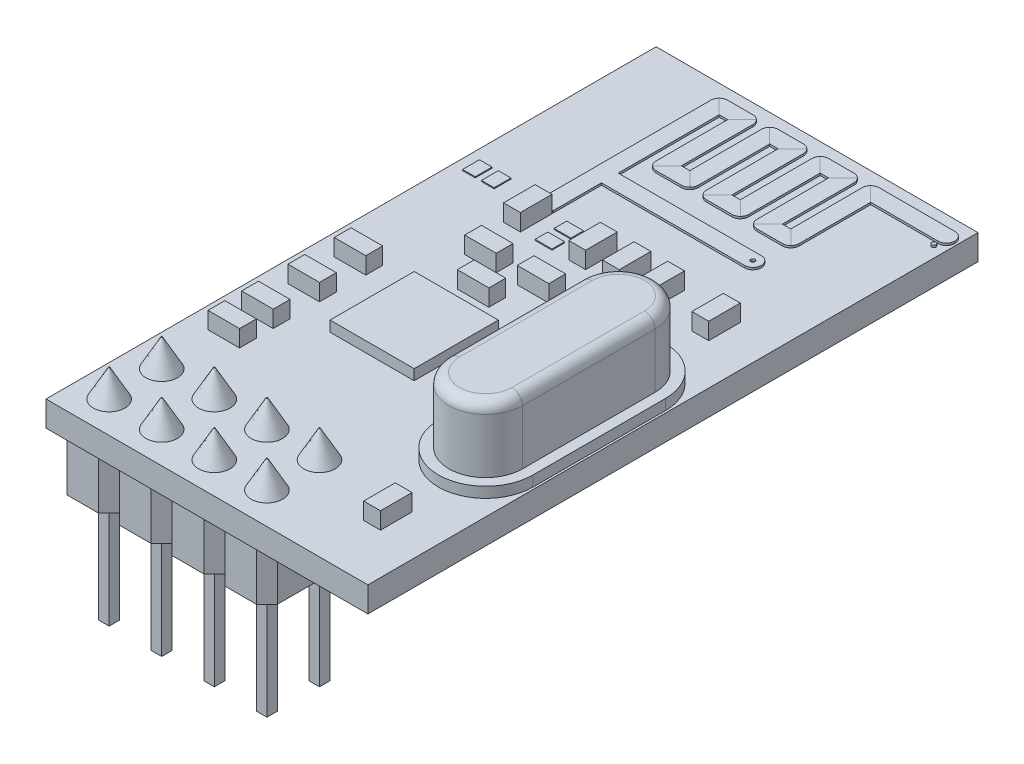
SolidWorks part; units mm, degrees
material "ABS"
ref_plane "정면" through (0, 0, 0) normal (0, 0, 1) x (1, 0, 0)
ref_plane "윗면" through (0, 0, 0) normal (0, 1, 0) x (1, 0, 0)
ref_plane "우측면" through (0, 0, 0) normal (1, 0, 0) x (0, 0, -1)
sketch "스케치1" plane through (0, 0, 0) normal (0, 1, 0) x (1, 0, 0)
  line L1 (7.65, -14.5) -> (-7.65, -14.5)
  line L2 (7.65, -14.5) -> (7.65, 14.5)
  line L3 (7.65, 14.5) -> (-7.65, 14.5)
  line L4 (-7.65, -14.5) -> (-7.65, 14.5)
  line L5 (7.65, -14.5) -> (-7.65, 14.5) construction
  line L6 (7.65, 14.5) -> (-7.65, -14.5) construction
  point P0 (0, 0)
  dimension "D1" = 15.3
  dimension "D2" = 29
extrude "보스-돌출1" add sketch "스케치1" along normal blind 1.2
sketch "스케치2" plane through (0, 1.2, 0) normal (0, 1, 0) x (1, 0, 0)
  line L0 (-7.65, 14.5) -> (-7.65, -14.5) construction
  line L1 (-7.65, -14.5) -> (7.65, -14.5) construction
  circle A0 centre (-6.15, -13) radius 0.75
  point P2 (-6.2469, -13.1386)
  dimension "D1" = 1.5
  dimension "D2" = 1.5
  dimension "D3" = 1.5
extrude "보스-돌출2" add sketch "스케치2" along normal blind 1.3
chamfer "모따기1" distance 1.3 angle 29 1 edges at (-6.15, 2.5, 13.75) first distance on face at (-6.15, 2.5, 13.75)
pattern_linear "선형 패턴1" count 4 spacing 2.5 along (1, 0, 0) count 2 spacing 2.5 along (0, 0, -1) of "보스-돌출2", "모따기1"
sketch "스케치3" plane through (0, 1.2, 0) normal (0, 1, 0) x (1, 0, 0)
  line L0 (-3.65, 5.2) -> (-3.65, 13.5)
  line L1 (-3.65, 13.5) -> (-2.45, 13.5)
  line L2 (-2.45, 13.5) -> (-2.45, 9.7)
  line L3 (-2.45, 9.7) -> (-1.25, 9.7)
  line L4 (-1.25, 9.7) -> (-1.25, 13.5)
  line L5 (-1.25, 13.5) -> (-0.05, 13.5)
  line L6 (-0.05, 13.5) -> (-0.05, 9.7)
  line L7 (-0.05, 9.7) -> (1.15, 9.7)
  line L8 (1.15, 9.7) -> (1.15, 13.5)
  line L9 (1.15, 13.5) -> (2.35, 13.5)
  line L10 (2.35, 13.5) -> (2.35, 9.7)
  line L11 (2.35, 9.7) -> (3.55, 9.7)
  line L12 (3.55, 9.7) -> (3.55, 13.5)
  line L13 (3.55, 13.5) -> (7.55, 13.5)
  line L14 (7.65, 14.5) -> (-7.65, 14.5) construction
  line L15 (7.65, -14.5) -> (7.65, 14.5) construction
  line L17 (-7.65, 14.5) -> (-7.65, -14.5) construction
  point P15 (-3.5057, 3.4598)
  point P17 (-2.4342, 13.6732)
  point P18 (6.8569, 13.6584)
  point P23 (4.6486, 13.5)
  point P24 (-3.5225, 13.5)
  point P25 (6.2398, 13.5)
  point P26 (4.1946, 13.5)
  point P27 (-3.3928, 13.4558)
  point P28 (2.6625, 9.4177)
  point P29 (0, 0)
  point P30 (-3.7935, 13.5)
  point P33 (-2.177, 13.5)
  point P34 (0, 13.5)
  point P35 (-0.899, 13.5)
  point P36 (1.3401, 13.5)
  point P37 (-1.1799, 13.5)
  dimension "D1" = 1
  dimension "D2" = 4
  dimension "D3" = 0.1
  dimension "D4" = 3.8
  dimension "D5" = 9.3
  dimension "D6" = 4
ref_plane "평면1" through (7.55, 0, 0) normal (1, 0, 0) x (0, 0, -1)
sketch "스케치4" plane through (7.55, 0, 0) normal (1, 0, 0) x (0, 0, -1)
  line L0 (13.5, 1.2) -> (9.7, 1.2) construction
  line L1 (13.9, 1.1) -> (13.1, 1.1)
  line L2 (13.9, 1.1) -> (13.9, 1.3)
  line L3 (13.9, 1.3) -> (13.1, 1.3)
  line L4 (13.1, 1.1) -> (13.1, 1.3)
  line L5 (13.9, 1.1) -> (13.1, 1.3) construction
  line L6 (13.9, 1.3) -> (13.1, 1.1) construction
  line L7 (-14.5, 1.2) -> (14.5, 1.2) construction
  point P0 (13.5, 1.2)
  point P9 (13.6993, 1.2)
  dimension "D1" = 0.1
  dimension "D2" = 0.8
sweep "스윕1" add profiles "스케치4" path "스케치3"
fillet "필렛1" radius 0.4 15 edges at (2.75, 1.25, -13.9) (0.75, 1.25, -13.9) (0.35, 1.25, -13.9) (-1.65, 1.25, -13.9) (-2.05, 1.25, -13.9) (-4.05, 1.25, -13.9) (-2.85, 1.25, -9.3) (-0.85, 1.25, -9.3) (-0.45, 1.25, -9.3) (1.55, 1.25, -9.3) (1.95, 1.25, -9.3) (3.95, 1.25, -9.3) (3.15, 1.25, -13.9) (7.55, 1.25, -13.1) (7.55, 1.25, -13.9)
sketch "스케치6" plane through (0, 1.2, 0) normal (0, 1, 0) x (1, 0, 0)
  line L0 (-3.25, 5.2) -> (-3.25, 13.1) construction
  line L1 (-3.25, 8.3) -> (3.55, 8.3)
  line L2 (-3.25, 8.3) -> (-3.25, 7.5)
  line L3 (-3.25, 7.5) -> (3.55, 7.5)
  line L5 (7.65, 14.5) -> (-7.65, 14.5) construction
  line L6 (3.95, 9.7) -> (3.95, 13.1) construction
  arc A0 (3.55, 7.5) -> (3.55, 8.3) centre (3.55, 7.9) ccw
  point P8 (0, 0)
  dimension "D1" = 0.8
  dimension "D2" = 7
extrude "보스-돌출3" add sketch "스케치6" along normal up to surface (0.1 mm away) up to face at (-3.7122, 1.3, -10.1589)
sketch "스케치7" plane through (0, 1.2, 0) normal (0, 1, 0) x (1, 0, 0)
  line L0 (7.15, 13.5) -> (7.15, 12.9) construction
  circle A0 centre (7.15, 12.9) radius 0.1
  point P2 (7.15, 13.5)
  dimension "D1" = 0.2
  dimension "D2" = 0.6
extrude "보스-돌출4" add sketch "스케치7" along normal up to surface (0.1 mm away) up to face at (5.4619, 1.3, -13.5518)
sketch "스케치8" plane through (0, 1.3, 0) normal (0, 1, 0) x (1, 0, 0)
  circle A0 centre (3.55, 7.9) radius 0.1
  circle A2 centre (7.15, 12.9) radius 0.1 construction
extrude "컷-돌출1" cut sketch "스케치8" against normal up to surface (0.1 mm away) up to face at (7.15, 1.2, -12.8)
sketch "스케치9" plane through (0, 1.2, 0) normal (0, 1, 0) x (1, 0, 0)
  line L0 (7.65, -14.5) -> (7.65, 14.5) construction
  line L2 (3.55, -0.25) -> (3.55, -6.55)
  line L4 (7.05, -0.25) -> (7.05, -6.55)
  line L5 (-7.65, -14.5) -> (7.65, -14.5) construction
  arc A0 (7.05, -0.25) -> (3.55, -0.25) centre (5.3, -0.25) ccw
  arc A1 (3.55, -6.55) -> (7.05, -6.55) centre (5.3, -6.55) ccw
  point P5 (5.3, 1.5)
  point P7 (5.3, -8.3)
  point P12 (6.65, -0.5904)
  point P13 (0, 0)
  point P14 (0, 0)
  dimension "D1" = 9.8
  dimension "D2" = 3.5
  dimension "D3" = 4.1
  dimension "D4" = 16
extrude "보스-돌출5" add sketch "스케치9" along normal blind 3.6
sketch "스케치10" plane through (0, 1.2, 0) normal (0, 1, 0) x (1, 0, 0)
  line L2 (3.05, -0.25) -> (3.05, -6.55)
  line L4 (7.55, -0.25) -> (7.55, -6.55)
  arc A0 (7.55, -0.25) -> (3.05, -0.25) centre (5.3, -0.25) ccw
  arc A1 (3.05, -6.55) -> (7.55, -6.55) centre (5.3, -6.55) ccw
  arc A2 (3.55, -6.55) -> (7.05, -6.55) centre (5.3, -6.55) ccw construction
  point P1 (4.9, -0.25)
  point P8 (7.1253, 0.2214)
  point P9 (0, 0)
  point P10 (2.65, -7.2177)
  point P11 (0, 0)
  dimension "D1" = 4.5
extrude "보스-돌출6" add sketch "스케치10" along normal blind 0.5
fillet "필렛2" radius 0.5 4 edges at (7.05, 4.8, 3.4) (5.3, 4.8, 8.3) (3.55, 4.8, 3.4) (5.3, 4.8, -1.5)
sketch "스케치11" plane through (0, 1.2, 0) normal (0, 1, 0) x (1, 0, 0)
  line L0 (-7.65, 14.5) -> (-7.65, -14.5) construction
  line L1 (-3.65, -1) -> (0.35, -1)
  line L2 (-3.65, -1) -> (-3.65, -5)
  line L3 (-3.65, -5) -> (0.35, -5)
  line L4 (0.35, -1) -> (0.35, -5)
  line L5 (-7.65, -14.5) -> (7.65, -14.5) construction
  dimension "D1" = 4
  dimension "D2" = 8
  dimension "D3" = 13.5
extrude "보스-돌출7" add sketch "스케치11" along normal blind 0.5
sketch "스케치12" plane through (0, 1.2, 0) normal (0, 1, 0) x (1, 0, 0)
  line L1 (-5.15, -7.8) -> (-6.65, -7.8)
  line L2 (-5.15, -7.8) -> (-5.15, -7)
  line L3 (-5.15, -7) -> (-6.65, -7)
  line L4 (-6.65, -7.8) -> (-6.65, -7)
  line L5 (-5.15, -7.8) -> (-6.65, -7) construction
  line L6 (-5.15, -7) -> (-6.65, -7.8) construction
  line L7 (-5.15, -6.2) -> (-6.65, -6.2)
  line L8 (-5.15, -6.2) -> (-5.15, -5.4)
  line L9 (-5.15, -5.4) -> (-6.65, -5.4)
  line L10 (-6.65, -6.2) -> (-6.65, -5.4)
  line L11 (-5.15, -6.2) -> (-6.65, -5.4) construction
  line L12 (-5.15, -5.4) -> (-6.65, -6.2) construction
  line L13 (-5.15, -4) -> (-6.65, -4)
  line L14 (-5.15, -4) -> (-5.15, -3.2)
  line L15 (-5.15, -3.2) -> (-6.65, -3.2)
  line L16 (-6.65, -4) -> (-6.65, -3.2)
  line L17 (-5.15, -4) -> (-6.65, -3.2) construction
  line L18 (-5.15, -3.2) -> (-6.65, -4) construction
  line L19 (-5.15, -1.8) -> (-6.65, -1.8)
  line L20 (-5.15, -1.8) -> (-5.15, -1)
  line L21 (-5.15, -1) -> (-6.65, -1)
  line L22 (-6.65, -1.8) -> (-6.65, -1)
  line L23 (-5.15, -1.8) -> (-6.65, -1) construction
  line L24 (-5.15, -1) -> (-6.65, -1.8) construction
  line L25 (-0.9, -0.2) -> (-2.4, -0.2)
  line L26 (-0.9, -0.2) -> (-0.9, 0.6)
  line L27 (-0.9, 0.6) -> (-2.4, 0.6)
  line L28 (-2.4, -0.2) -> (-2.4, 0.6)
  line L29 (-0.9, -0.2) -> (-2.4, 0.6) construction
  line L30 (-0.9, 0.6) -> (-2.4, -0.2) construction
  line L31 (-2.15, 1.4) -> (-3.65, 1.4)
  line L32 (-2.15, 1.4) -> (-2.15, 2.2)
  line L33 (-2.15, 2.2) -> (-3.65, 2.2)
  line L34 (-3.65, 1.4) -> (-3.65, 2.2)
  line L35 (-2.15, 1.4) -> (-3.65, 2.2) construction
  line L36 (-2.15, 2.2) -> (-3.65, 1.4) construction
  line L37 (0.35, 1.4) -> (-1.15, 1.4)
  line L38 (0.35, 1.4) -> (0.35, 2.2)
  line L39 (0.35, 2.2) -> (-1.15, 2.2)
  line L40 (-1.15, 1.4) -> (-1.15, 2.2)
  line L41 (0.35, 1.4) -> (-1.15, 2.2) construction
  line L42 (0.35, 2.2) -> (-1.15, 1.4) construction
  line L43 (5.7, 3.65) -> (4.9, 3.65)
  line L44 (5.7, 3.65) -> (5.7, 5.15)
  line L45 (5.7, 5.15) -> (4.9, 5.15)
  line L46 (4.9, 3.65) -> (4.9, 5.15)
  line L47 (5.7, 3.65) -> (4.9, 5.15) construction
  line L48 (5.7, 5.15) -> (4.9, 3.65) construction
  line L49 (3.05, 3.65) -> (2.25, 3.65)
  line L50 (3.05, 3.65) -> (3.05, 5.15)
  line L51 (3.05, 5.15) -> (2.25, 5.15)
  line L52 (2.25, 3.65) -> (2.25, 5.15)
  line L53 (3.05, 3.65) -> (2.25, 5.15) construction
  line L54 (3.05, 5.15) -> (2.25, 3.65) construction
  line L55 (1.45, 3.65) -> (0.65, 3.65)
  line L56 (1.45, 3.65) -> (1.45, 5.15)
  line L57 (1.45, 5.15) -> (0.65, 5.15)
  line L58 (0.65, 3.65) -> (0.65, 5.15)
  line L59 (1.45, 3.65) -> (0.65, 5.15) construction
  line L60 (1.45, 5.15) -> (0.65, 3.65) construction
  line L61 (-0.15, 3.65) -> (-0.95, 3.65)
  line L62 (-0.15, 3.65) -> (-0.15, 5.15)
  line L63 (-0.15, 5.15) -> (-0.95, 5.15)
  line L64 (-0.95, 3.65) -> (-0.95, 5.15)
  line L65 (-0.15, 3.65) -> (-0.95, 5.15) construction
  line L66 (-0.15, 5.15) -> (-0.95, 3.65) construction
  line L67 (-3.25, 3.65) -> (-4.05, 3.65)
  line L68 (-3.25, 3.65) -> (-3.25, 5.15)
  line L69 (-3.25, 5.15) -> (-4.05, 5.15)
  line L70 (-4.05, 3.65) -> (-4.05, 5.15)
  line L71 (-3.25, 3.65) -> (-4.05, 5.15) construction
  line L72 (-3.25, 5.15) -> (-4.05, 3.65) construction
  line L73 (-3.25, 5.2) -> (-3.25, 7.5) construction
  line L74 (-4.05, 5.2) -> (-4.05, 13.5) construction
  line L75 (0.35, -1) -> (-3.65, -1) construction
  line L76 (-1.65, 0.2) -> (-1.65, -1) construction
  line L77 (-2.15, 1.8) -> (-1.15, 1.8) construction
  line L78 (-1.65, 1.8) -> (-1.65, 0.6) construction
  line L79 (0.35, -1) -> (-3.65, -1) construction
  line L80 (-7.65, 14.5) -> (-7.65, -14.5) construction
  line L81 (5.7, -11.95) -> (4.9, -11.95)
  line L82 (5.7, -11.95) -> (5.7, -10.45)
  line L83 (5.7, -10.45) -> (4.9, -10.45)
  line L84 (4.9, -11.95) -> (4.9, -10.45)
  line L85 (5.7, -11.95) -> (4.9, -10.45) construction
  line L86 (5.7, -10.45) -> (4.9, -11.95) construction
  line L87 (5.3, 4.4) -> (5.3, -0.25) construction
  line L88 (5.3, -6.55) -> (5.3, -11.2) construction
  line L89 (-4.05, 5.2) -> (-3.25, 5.2) construction
  point P0 (-5.9, -7.4)
  point P5 (-5.9, -5.8)
  point P10 (-5.9, -3.6)
  point P15 (-5.9, -1.4)
  point P20 (-1.65, 0.2)
  point P25 (-2.9, 1.8)
  point P30 (-0.4, 1.8)
  point P35 (5.3, 4.4)
  point P40 (2.65, 4.4)
  point P45 (1.05, 4.4)
  point P50 (-0.55, 4.4)
  point P55 (-3.65, 4.4)
  point P60 (-4.05, 5.0796)
  point P68 (-1.65, -1)
  point P70 (5.3, -0.25)
  point P79 (5.3, -6.55)
  point P82 (5.3, -11.2)
  point P88 (-5.9, -4)
  dimension "D1" = 1.5
  dimension "D2" = 0.8
  dimension "D3" = 0.8
  dimension "D4" = 2.3
  dimension "D5" = 0.8
  dimension "D6" = 0.8
  dimension "D7" = 1
  dimension "D8" = 2.5
  dimension "D9" = 0.8
  dimension "D10" = 1.4
  dimension "D11" = 1.4
  dimension "D12" = 0.05
extrude "보스-돌출8" add sketch "스케치12" along normal blind 0.8
sketch "스케치13" plane through (0, 1.2, 0) normal (0, 1, 0) x (1, 0, 0)
  line L0 (-3.25, 5.15) -> (-4.05, 5.15) construction
  line L1 (-2.55, 5.15) -> (-1.75, 5.15)
  line L2 (-2.55, 5.15) -> (-2.55, 4.55)
  line L3 (-2.55, 4.55) -> (-1.75, 4.55)
  line L4 (-1.75, 5.15) -> (-1.75, 4.55)
  line L5 (-2.55, 4.25) -> (-1.75, 4.25)
  line L6 (-2.55, 4.25) -> (-2.55, 3.65)
  line L7 (-2.55, 3.65) -> (-1.75, 3.65)
  line L8 (-1.75, 4.25) -> (-1.75, 3.65)
  line L9 (-5.65, 5.6) -> (-6.25, 5.6)
  line L10 (-5.65, 5.6) -> (-5.65, 4.8)
  line L11 (-5.65, 4.8) -> (-6.25, 4.8)
  line L12 (-6.25, 5.6) -> (-6.25, 4.8)
  line L13 (-6.55, 5.6) -> (-7.15, 5.6)
  line L14 (-6.55, 5.6) -> (-6.55, 4.8)
  line L15 (-6.55, 4.8) -> (-7.15, 4.8)
  line L16 (-7.15, 5.6) -> (-7.15, 4.8)
  line L17 (-4.05, 3.65) -> (-3.25, 3.65) construction
  line L18 (-0.95, 5.15) -> (-0.95, 3.65) construction
  line L19 (-7.65, 14.5) -> (-7.65, -14.5) construction
  line L20 (-4.05, 5.2) -> (-5.65, 5.2) construction
  point P20 (-6.3435, 5.6)
  dimension "D1" = 0.8
  dimension "D2" = 0.8
  dimension "D3" = 0.6
  dimension "D4" = 0.5
  dimension "D5" = 1.5
extrude "보스-돌출9" add sketch "스케치13" along normal blind 0.05
sketch "스케치14" plane through (0, 0, 0) normal (0, -1, 0) x (1, 0, 0)
  line L0 (-6.9, 14.25) -> (-7.4, 13.75)
  line L1 (-7.4, 13.75) -> (-7.4, 9.75)
  line L2 (-7.4, 9.75) -> (-6.9, 9.25)
  line L3 (-6.9, 9.25) -> (-5.4, 9.25)
  line L4 (-5.4, 9.25) -> (-4.9, 9.75)
  line L5 (-4.9, 9.75) -> (-4.9, 13.75)
  line L6 (-4.9, 13.75) -> (-5.4, 14.25)
  line L7 (-5.4, 14.25) -> (-6.9, 14.25)
  line L8 (-6.15, 14.25) -> (-6.15, 13) construction
  dimension "D1" = 135
  dimension "D2" = 2.5
  dimension "D3" = 5
  dimension "D4" = 0.5
  dimension "D5" = 1.25
extrude "보스-돌출10" add sketch "스케치14" along normal blind 2.5
sketch "스케치15" plane through (0, -2.5, 0) normal (0, -1, 0) x (1, 0, 0)
  line L1 (-5.9, 12.75) -> (-6.4, 12.75)
  line L2 (-5.9, 12.75) -> (-5.9, 13.25)
  line L3 (-5.9, 13.25) -> (-6.4, 13.25)
  line L4 (-6.4, 12.75) -> (-6.4, 13.25)
  line L5 (-5.9, 12.75) -> (-6.4, 13.25) construction
  line L6 (-5.9, 13.25) -> (-6.4, 12.75) construction
  line L7 (-5.9, 10.25) -> (-6.4, 10.25)
  line L8 (-5.9, 10.25) -> (-5.9, 10.75)
  line L9 (-5.9, 10.75) -> (-6.4, 10.75)
  line L10 (-6.4, 10.25) -> (-6.4, 10.75)
  line L11 (-5.9, 10.25) -> (-6.4, 10.75) construction
  line L12 (-5.9, 10.75) -> (-6.4, 10.25) construction
  point P0 (-6.15, 13)
  point P6 (-6.15, 10.5)
  dimension "D1" = 0.5
  dimension "D2" = 2.5
extrude "보스-돌출11" add sketch "스케치15" along normal blind 5.5
chamfer "모따기2" distance 0.1 angle 45 8 edges at (-6.15, -8, 10.75) (-5.9, -8, 10.5) (-6.15, -8, 10.25) (-6.4, -8, 10.5) (-6.15, -8, 13.25) (-5.9, -8, 13) (-6.15, -8, 12.75) (-6.4, -8, 13)
pattern_linear "선형 패턴2" count 4 spacing 2.5 along (1, 0, 0) of "보스-돌출10"
pattern_linear "선형 패턴3" count 4 spacing 2.5 along (1, 0, 0) of "보스-돌출11", "모따기2"
sketch "스케치16" plane through (0, 0, 0) normal (0, -1, 0) x (1, 0, 0)
  circle A0 centre (5.3, 6.55) radius 0.75
  circle A1 centre (5.3, 0.25) radius 0.75
  dimension "D1" = 1.5
extrude "보스-돌출12" add sketch "스케치16" along normal blind 1.3
chamfer "모따기3" distance 1.3 angle 29 2 edges at (5.3, -1.3, -0.5) (5.3, -1.3, 5.8) first distance on face at (5.3, -1.3, -0.5) first distance on face at (5.3, -1.3, 5.8)
